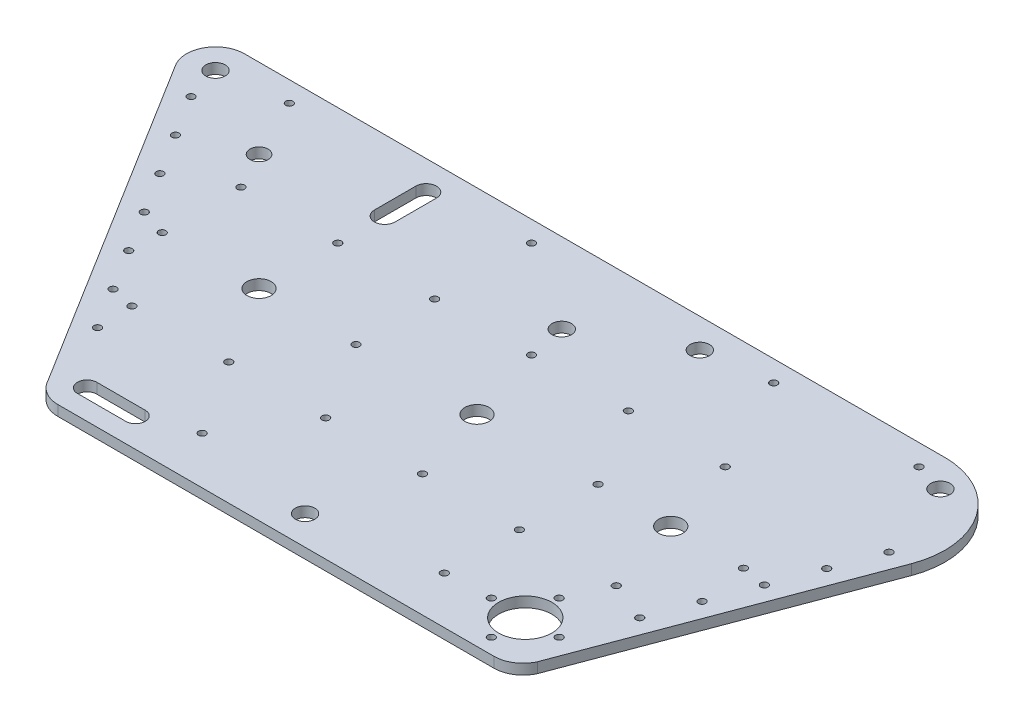
SolidWorks part; units mm, degrees
ref_plane "Front Plane" through (0, 0, 0) normal (0, 0, 1) x (1, 0, 0)
ref_plane "Top Plane" through (0, 0, 0) normal (0, 1, 0) x (1, 0, 0)
ref_plane "Right Plane" through (0, 0, 0) normal (1, 0, 0) x (0, 0, -1)
sketch "Sketch1" plane through (0, 0, 0) normal (0, 1, 0) x (1, 0, 0)
  line L0 (-49.6282, 67.8579) -> (85.6574, 67.9768)
  line L1 (75.3712, -8.8952) -> (-8.8947, -8.8952)
  line L2 (80.478, -5.618) -> (100.2202, 46.9723)
  line L3 (-8.8947, -1.4045) -> (0.4681, -1.4045)
  line L4 (0.4681, -5.1498) -> (-8.8947, -5.1498)
  line L5 (-13.9046, -5.8187) -> (-54.3474, 59.2753)
  line L6 (-8.8947, -8.427) -> (-8.8375, -8.4267)
  line L9 (-10.8947, 62.2663) -> (-10.8947, 54.2663)
  line L10 (-6.8947, 62.2663) -> (-6.8947, 54.2663)
  arc A0 (-6.8947, 62.2663) -> (-10.8947, 62.2663) centre (-8.8947, 62.2663) ccw
  arc A1 (-10.8947, 54.2663) -> (-6.8947, 54.2663) centre (-8.8947, 54.2663) ccw
  ellipse E0 centre (-49.6233, 62.2663) end of major axis (-49.6233, 64.1389) minor radius 1.8726
  ellipse E1 centre (71.9307, 0.5932) end of major axis (71.9307, 5.743) minor radius 5.1496
  ellipse E2 centre (-8.8947, -3.2772) end of major axis (-8.8947, -5.1498) minor radius 1.8726 (-8.8947, -1.4045) -> (-8.8947, -5.1498) ccw
  ellipse E3 centre (71.9307, 7.1475) end of major axis (71.9307, 7.8498) minor radius 0.7022
  ellipse E4 centre (-49.6233, 62.2663) end of major axis (-49.6233, 67.8579) minor radius 5.5913 (-49.6282, 67.8579) -> (-54.3474, 59.2753) ccw
  ellipse E5 centre (85.6704, 52.4348) end of major axis (85.6704, 67.9768) minor radius 15.5413 (100.2202, 46.9723) -> (85.6567, 67.9768) ccw
  ellipse E6 centre (0.4681, -3.2772) end of major axis (0.4681, -5.1498) minor radius 1.8726 (0.4681, -5.1498) -> (0.4681, -1.4045) ccw
  ellipse E7 centre (78.4847, 0.5932) end of major axis (78.4847, 1.2954) minor radius 0.7022
  ellipse E8 centre (65.3766, 0.5932) end of major axis (65.3766, 1.2954) minor radius 0.7022
  ellipse E9 centre (71.9307, -5.9612) end of major axis (71.9307, -6.6634) minor radius 0.7022
  ellipse E10 centre (90.5108, 62.2663) end of major axis (90.5108, 64.1389) minor radius 1.8726
  ellipse E11 centre (-8.8947, -3.2772) end of major axis (-8.8947, 2.3408) minor radius 5.6177 (-13.9055, -5.8173) -> (-8.8947, -8.8952) ccw
  ellipse E12 centre (75.3712, -3.2772) end of major axis (75.3712, 2.3408) minor radius 5.6177 (75.3712, -8.8952) -> (80.478, -5.618) ccw
  ellipse E13 centre (56.6454, 0.2341) end of major axis (56.6454, 0.9363) minor radius 0.7022
  ellipse E14 centre (9.831, 0.2341) end of major axis (9.831, 0.9363) minor radius 0.7022
  ellipse E15 centre (56.6454, 29.9627) end of major axis (56.6454, 30.665) minor radius 0.7022
  ellipse E16 centre (9.831, 29.9627) end of major axis (9.831, 30.665) minor radius 0.7022
  ellipse E17 centre (-27.6205, 29.9627) end of major axis (-27.6205, 30.665) minor radius 0.7022
  ellipse E18 centre (84.7341, 29.9627) end of major axis (84.7341, 30.665) minor radius 0.7022
  ellipse E19 centre (-36.9834, 63.9049) end of major axis (-36.9834, 64.6071) minor radius 0.7022
  ellipse E20 centre (9.831, 63.9049) end of major axis (9.831, 64.6071) minor radius 0.7022
  ellipse E21 centre (56.6454, 63.9049) end of major axis (56.6454, 64.6071) minor radius 0.7022
  ellipse E22 centre (28.5568, 45.1782) end of major axis (28.5568, 45.8804) minor radius 0.7022
  ellipse E23 centre (66.0083, 45.1782) end of major axis (66.0083, 45.8804) minor radius 0.7022
  ellipse E24 centre (75.3712, 14.7473) end of major axis (75.3712, 15.4495) minor radius 0.7022
  ellipse E25 centre (37.9197, 14.7473) end of major axis (37.9197, 14.045) minor radius 0.7022
  ellipse E26 centre (-8.8947, 45.1782) end of major axis (-8.8947, 45.8804) minor radius 0.7022
  ellipse E27 centre (-18.2576, 14.7473) end of major axis (-18.2576, 14.045) minor radius 0.7022
  ellipse E28 centre (-8.8947, 29.9627) end of major axis (-8.8947, 27.6219) minor radius 2.3407
  ellipse E29 centre (33.2382, 29.9627) end of major axis (33.2382, 27.6219) minor radius 2.3407
  ellipse E30 centre (70.6898, 29.9627) end of major axis (70.6898, 27.6219) minor radius 2.3407
  ellipse E31 centre (-47.6076, 55.5239) end of major axis (-47.6076, 54.8217) minor radius 0.7022
  ellipse E32 centre (-42.6663, 47.5708) end of major axis (-42.6663, 48.273) minor radius 0.7022
  ellipse E33 centre (-37.7251, 39.6177) end of major axis (-37.7251, 38.9155) minor radius 0.7022
  ellipse E34 centre (-32.7836, 31.6644) end of major axis (-32.7836, 32.3666) minor radius 0.7022
  ellipse E35 centre (-27.8423, 23.7111) end of major axis (-27.8423, 24.4133) minor radius 0.7022
  ellipse E36 centre (-22.901, 15.7579) end of major axis (-22.901, 15.0557) minor radius 0.7022
  ellipse E37 centre (-17.9598, 7.8049) end of major axis (-17.9598, 8.5072) minor radius 0.7022
  ellipse E38 centre (96.1253, 46.7211) end of major axis (96.1253, 46.0189) minor radius 0.7022
  ellipse E39 centre (92.8491, 37.9497) end of major axis (92.8491, 38.652) minor radius 0.7022
  ellipse E40 centre (89.5728, 29.1784) end of major axis (89.5728, 28.4762) minor radius 0.7022
  ellipse E41 centre (86.2966, 20.4072) end of major axis (86.2966, 19.705) minor radius 0.7022
  ellipse E42 centre (83.0205, 11.636) end of major axis (83.0205, 12.3383) minor radius 0.7022
  ellipse E44 centre (84.7341, 63.9049) end of major axis (84.7341, 64.6071) minor radius 0.7022
  ellipse E45 centre (9.831, 45.1782) end of major axis (9.831, 45.8804) minor radius 0.7022
  ellipse E46 centre (47.2826, 45.1782) end of major axis (47.2826, 45.8804) minor radius 0.7022
  ellipse E47 centre (-27.6205, 45.1782) end of major axis (-27.6205, 45.8804) minor radius 0.7022
  ellipse E48 centre (0.4681, 14.7473) end of major axis (0.4681, 15.4495) minor radius 0.7022
  ellipse E49 centre (19.1939, 14.7473) end of major axis (19.1939, 14.045) minor radius 0.7022
  ellipse E50 centre (56.6454, 14.7473) end of major axis (56.6454, 15.4495) minor radius 0.7022
  ellipse E51 centre (-31.3657, 52.4348) end of major axis (-31.3657, 54.1904) minor radius 1.7555
  ellipse E52 centre (27.1524, 52.4348) end of major axis (27.1524, 54.3074) minor radius 1.8726
  ellipse E54 centre (44.0055, 62.2663) end of major axis (44.0055, 64.1389) minor radius 1.8726
  ellipse E55 centre (33.2382, -3.2772) end of major axis (33.2382, -1.4045) minor radius 1.8726
  dimension "D2" = 8
extrude "Boss-Extrude1" add sketch "Sketch1" along normal blind 2 contours L1 E12 L2 E5 L0 E4 L5 E11 E55 E54 E52 E51 E50 E49 E48 E47 E46 E45 E44 E42 E41 E40 E39 E38 E37 E36 region at (27.7747, 0, -33.1666)
